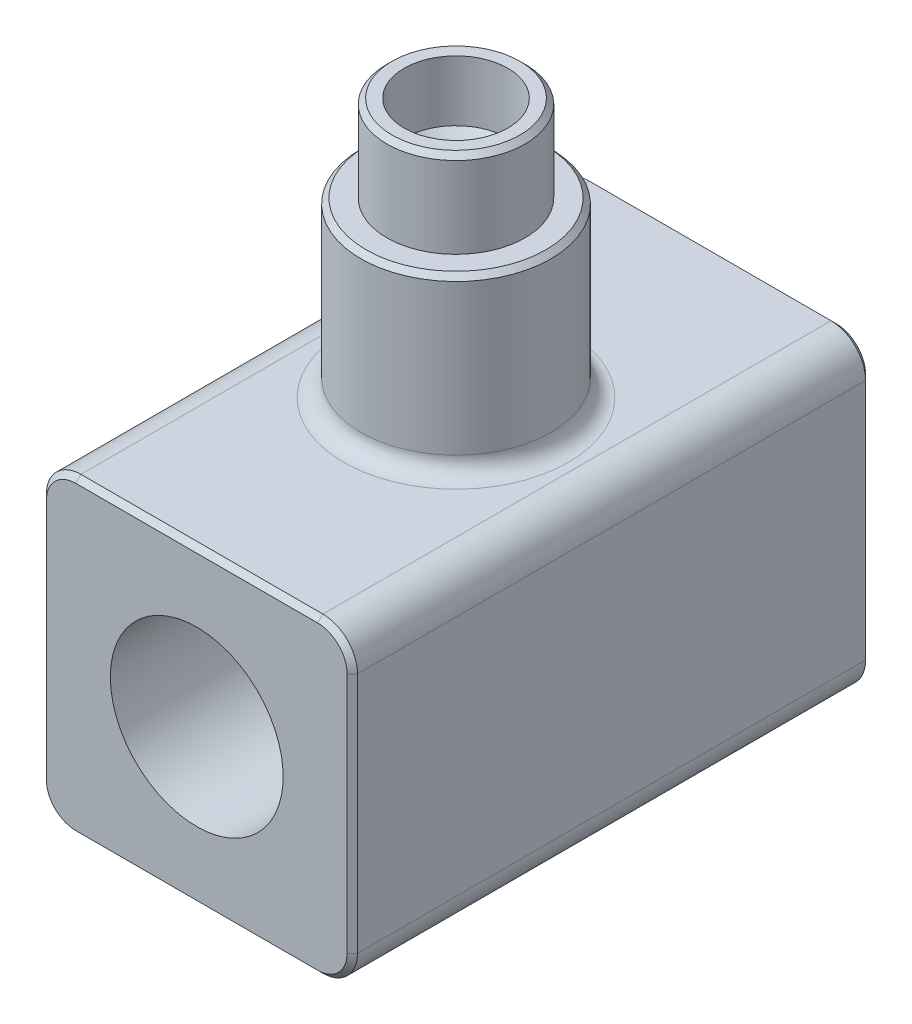
SolidWorks part; units mm, degrees
ref_plane "Front Plane" through (0, 0, 0) normal (0, 0, 1) x (1, 0, 0)
ref_plane "Top Plane" through (0, 0, 0) normal (0, 1, 0) x (1, 0, 0)
ref_plane "Right Plane" through (0, 0, 0) normal (1, 0, 0) x (0, 0, -1)
sketch "Sketch1" plane through (0, 0, 0) normal (0, 0, 1) x (1, 0, 0)
  line L1 (9, -9) -> (-9, -9)
  line L2 (9, -9) -> (9, 9)
  line L3 (9, 9) -> (-9, 9)
  line L4 (-9, -9) -> (-9, 9)
  line L5 (9, -9) -> (-9, 9) construction
  line L6 (9, 9) -> (-9, -9) construction
  point P0 (0, 0)
  dimension "D1" = 18
  dimension "D2" = 18
extrude "Boss-Extrude1" add sketch "Sketch1" along normal blind 30
fillet "Fillet1" radius 2 4 edges at (9, -9, 15) (-9, -9, 15) (9, 9, 15) (-9, 9, 15)
sketch "Sketch2" plane through (0, 0, 0) normal (0, 0, -1) x (-1, 0, 0)
  circle A0 centre (0, 0) radius 5
  dimension "D1" = 10
extrude "Cut-Extrude1" cut sketch "Sketch2" against normal blind 12
ref_plane "Plane1" through (0, 0, 15) normal (0, 0, 1) x (1, 0, 0)
mirror "Mirror1" about plane through (0, 0, 15) normal (0, 0, 1) of "Cut-Extrude1"
sketch "Sketch3" plane through (0, 9, 0) normal (0, 1, 0) x (1, 0, 0)
  line L0 (0, 0) -> (0, -15) construction
  line L1 (7, -30) -> (-7, -30) construction
  circle A0 centre (0, -15) radius 5.5
  dimension "D1" = 11
  dimension "D2" = 15
extrude "Boss-Extrude2" add sketch "Sketch3" along normal blind 10
sketch "Sketch4" plane through (0, 19, 0) normal (0, 1, 0) x (1, 0, 0)
  circle A0 centre (0, -15) radius 4
  dimension "D1" = 8
extrude "Boss-Extrude3" add sketch "Sketch4" along normal blind 5
sketch "Sketch5" plane through (0, 24, 0) normal (0, 1, 0) x (1, 0, 0)
  circle A0 centre (0, -15) radius 3
  dimension "D1" = 6
extrude "Cut-Extrude2" cut sketch "Sketch5" against normal blind 3
sketch "Sketch6" plane through (0, 21, 0) normal (0, 1, 0) x (1, 0, 0)
  circle A0 centre (0, -15) radius 1.5
  dimension "D1" = 3
extrude "Cut-Extrude3" cut sketch "Sketch6" against normal blind 19
chamfer "Chamfer1" distance 2 angle 45 1 edges at (-1.5, 21, 15)
fillet "Fillet2" radius 1 1 edges at (5.5, 9, 15)
sketch "Sketch7" plane through (0, 0, 12) normal (0, 0, -1) x (-1, 0, 0)
  circle A0 centre (0, 0) radius 1.5
  dimension "D1" = 3
extrude "Cut-Extrude4" cut sketch "Sketch7" against normal through all
chamfer "Chamfer2" distance 0.3 angle 45 18 edges at (-4, 24, 15) (-5.5, 19, 15) (-9, 0, 30) (-8.4142, -8.4142, 30) (-8.4142, 8.4142, 30) (0, -9, 30) (0, 9, 30) (8.4142, -8.4142, 30) (8.4142, 8.4142, 30) (9, 0, 30) (-9, 0, 0) (-8.4142, -8.4142, 0) (-8.4142, 8.4142, 0) (0, -9, 0) (0, 9, 0) (8.4142, -8.4142, 0) (8.4142, 8.4142, 0) (9, 0, 0)
